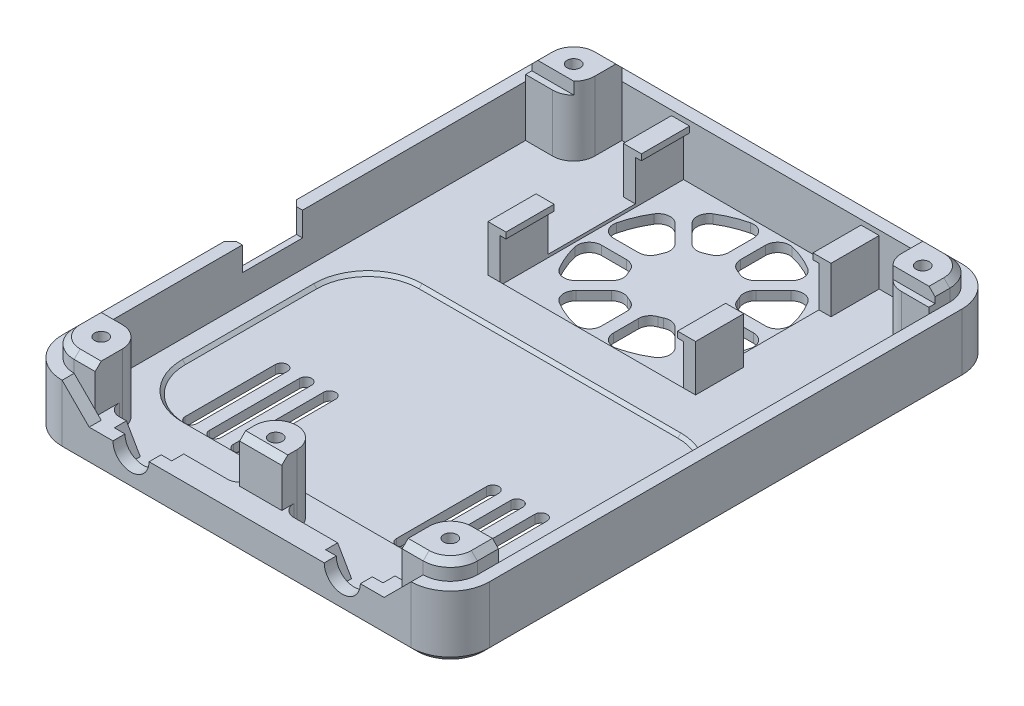
SolidWorks part; units mm, degrees
ref_plane "Front Plane" through (0, 0, 0) normal (0, 0, 1) x (1, 0, 0)
ref_plane "Top Plane" through (0, 0, 0) normal (0, 1, 0) x (1, 0, 0)
ref_plane "Right Plane" through (0, 0, 0) normal (1, 0, 0) x (0, 0, -1)
sketch "Sketch1" plane through (0, 0, 0) normal (0, 1, 0) x (1, 0, 0)
  line L0 (-33.8462, -25.5532) -> (31.1538, -25.5532)
  line L1 (-33.8462, 38.4468) -> (31.1538, 38.4468)
  line L2 (-33.8462, 38.4468) -> (-33.8462, 8.4468)
  line L3 (-33.8462, 8.4468) -> (31.1538, 8.4468)
  line L4 (31.1538, 38.4468) -> (31.1538, 8.4468)
  line L5 (-30.3462, 34.9468) -> (27.6538, 34.9468)
  line L6 (-30.3462, 34.9468) -> (-30.3462, 11.9468)
  line L7 (-30.3462, 11.9468) -> (27.6538, 11.9468)
  line L8 (27.6538, 34.9468) -> (27.6538, 11.9468)
  line L9 (-30.3462, 0.9468) -> (27.6538, 0.9468)
  line L10 (-30.3462, 0.9468) -> (-30.3462, -22.0532)
  line L11 (-33.8462, 4.4468) -> (31.1538, 4.4468)
  line L12 (-33.8462, 4.4468) -> (-33.8462, -25.5532)
  line L13 (-30.3462, -22.0532) -> (27.6538, -22.0532)
  line L14 (31.1538, 4.4468) -> (31.1538, -25.5532)
  line L15 (27.6538, 0.9468) -> (27.6538, -22.0532)
  line L16 (-37.9161, 25.3468) -> (-35.3276, 25.3468)
  line L17 (7.5538, 7.5472) -> (7.5538, 6.2645)
  line L18 (20.1538, 7.5472) -> (20.1538, 6.2645)
  dimension "D1" = 65
  dimension "D2" = 30
  dimension "D3" = 58
  dimension "D4" = 23
  dimension "D5" = 3.5
  dimension "D6" = 3.5
  dimension "D7" = 65
  dimension "D8" = 30
  dimension "D9" = 58
  dimension "D10" = 23
  dimension "D11" = 3.5
  dimension "D12" = 3.5
  dimension "D13" = 4
  dimension "D14" = 16.9
  dimension "D15" = 41.4
  dimension "D16" = 54
sketch "Sketch2" plane through (0, 0, 0) normal (0, 1, 0) x (1, 0, 0)
  line L0 (-33.8462, 38.4468) -> (-33.8462, 8.4468) construction
  line L1 (-30.3462, 39.4468) -> (27.6538, 39.4468)
  line L2 (-34.8462, 34.9468) -> (-34.8462, -43.5532)
  line L3 (-30.3462, -48.0532) -> (27.6538, -48.0532)
  line L4 (32.1538, 34.9468) -> (32.1538, -43.5532)
  line L5 (-33.8462, 38.4468) -> (31.1538, 38.4468) construction
  line L6 (31.1538, 38.4468) -> (31.1538, 8.4468) construction
  line L7 (-30.3462, 41.4468) -> (27.6538, 41.4468)
  line L8 (34.1538, 34.9468) -> (34.1538, -43.5532)
  line L9 (-30.3462, -50.0532) -> (27.6538, -50.0532)
  line L10 (-36.8462, 34.9468) -> (-36.8462, -43.5532)
  line L11 (-34.8462, 39.4468) -> (32.1538, 39.4468) construction
  line L12 (-34.8462, 39.4468) -> (-34.8462, -48.0532) construction
  line L13 (-36.8462, 41.4468) -> (-36.8462, -50.0532) construction
  line L14 (-36.8462, 41.4468) -> (34.1538, 41.4468) construction
  line L15 (32.1538, 39.4468) -> (32.1538, -48.0532) construction
  line L16 (34.1538, 41.4468) -> (34.1538, -50.0532) construction
  line L17 (-36.8462, -50.0532) -> (34.1538, -50.0532) construction
  line L18 (-34.8462, -48.0532) -> (32.1538, -48.0532) construction
  arc A0 (-30.3462, 39.4468) -> (-34.8462, 34.9468) centre (-30.3462, 34.9468) ccw
  arc A1 (-36.8462, 34.9468) -> (-30.3462, 41.4468) centre (-30.3462, 34.9468) cw
  arc A2 (32.1538, 34.9468) -> (27.6538, 39.4468) centre (27.6538, 34.9468) ccw
  arc A3 (34.1538, 34.9468) -> (27.6538, 41.4468) centre (27.6538, 34.9468) ccw
  arc A4 (27.6538, -50.0532) -> (34.1538, -43.5532) centre (27.6538, -43.5532) ccw
  arc A5 (-36.8462, -43.5532) -> (-30.3462, -50.0532) centre (-30.3462, -43.5532) ccw
  arc A6 (27.6538, -48.0532) -> (32.1538, -43.5532) centre (27.6538, -43.5532) ccw
  arc A7 (-30.3462, -48.0532) -> (-34.8462, -43.5532) centre (-30.3462, -43.5532) cw
  dimension "D6" = 4.5
  dimension "D7" = 6.5
  dimension "D8" = 4.5
  dimension "D9" = 6.5
  dimension "D10" = 6.5
  dimension "D11" = 4.5
  dimension "D1" = 1
  dimension "D2" = 1
  dimension "D3" = 1
  dimension "D4" = 87.5
  dimension "D5" = 2
extrude "Boss-Extrude1" add sketch "Sketch2" along normal blind 10.5
sketch "Sketch3" plane through (0, 0, 0) normal (0, 1, 0) x (1, 0, 0)
  line L0 (-30.3462, -48.0532) -> (27.6538, -48.0532)
  line L1 (-30.3462, 39.4468) -> (27.6538, 39.4468)
  line L2 (-34.8462, 34.9468) -> (-34.8462, -43.5532)
  line L4 (32.1538, 34.9468) -> (32.1538, -43.5532)
  arc A0 (27.6538, -48.0532) -> (32.1538, -43.5532) centre (27.6538, -43.5532) ccw
  arc A1 (-34.8462, -43.5532) -> (-30.3462, -48.0532) centre (-30.3462, -43.5532) ccw
  arc A2 (32.1538, 34.9468) -> (27.6538, 39.4468) centre (27.6538, 34.9468) ccw
  arc A3 (-30.3462, 39.4468) -> (-34.8462, 34.9468) centre (-30.3462, 34.9468) ccw
  point P15 (-34.8462, 39.4468)
  dimension "D1" = 4.5
  dimension "D2" = 87.5
extrude "Boss-Extrude2" add sketch "Sketch3" along normal blind 2
sketch "Sketch6" plane through (0, 2, 0) normal (0, 1, 0) x (1, 0, 0)
  line L3 (-34.8462, 34.9468) -> (-34.8462, -43.5532) construction
  line L5 (-26.8462, 34.9468) -> (-26.8462, 39.4468)
  line L6 (27.6538, 39.4468) -> (-30.3462, 39.4468) construction
  line L7 (-26.8462, 39.4468) -> (-30.3462, 39.4468)
  line L8 (-30.3462, 31.4468) -> (-34.8462, 31.4468)
  line L9 (-34.8462, 31.4468) -> (-34.8462, 34.9468)
  line L10 (24.1538, 34.9468) -> (24.1538, 39.4468)
  line L11 (24.1538, 39.4468) -> (27.6538, 39.4468)
  line L12 (27.6538, 31.4468) -> (32.1538, 31.4468)
  line L13 (32.1538, -43.5532) -> (32.1538, 34.9468) construction
  line L14 (32.1538, 31.4468) -> (32.1538, 34.9468)
  arc A0 (-30.3462, 31.4468) -> (-26.8462, 34.9468) centre (-30.3462, 34.9468) ccw
  arc A1 (24.1538, 34.9468) -> (27.6538, 31.4468) centre (27.6538, 34.9468) ccw
  arc A4 (-30.3462, 39.4468) -> (-34.8462, 34.9468) centre (-30.3462, 34.9468) ccw
  arc A5 (32.1538, 34.9468) -> (27.6538, 39.4468) centre (27.6538, 34.9468) ccw
  dimension "D1" = 4.5
  dimension "D2" = 4.5
extrude "Boss-Extrude4" add sketch "Sketch6" along normal blind 11.5
sketch "Sketch7" plane through (0, 0, 50.0532) normal (0, 0, 1) x (1, 0, 0)
  line L0 (27.6538, 10.5) -> (-30.3462, 10.5)
  line L2 (16.2046, 6) -> (16.2046, 3) construction
  line L3 (-18.8969, 6) -> (-18.8969, 3) construction
  line L4 (-1.3462, 10.5) -> (-1.3462, 13.2512) construction
  line L5 (-30.3462, 10.5) -> (27.6538, 10.5) construction
  line L20 (27.6538, 10.5) -> (23.1538, 6)
  line L21 (23.1538, 6) -> (19.2046, 6)
  line L22 (13.2046, 6) -> (-15.8969, 6)
  line L23 (-25.8462, 6) -> (-21.8969, 6)
  line L24 (-30.3462, 10.5) -> (-25.8462, 6)
  arc A0 (-21.8969, 6) -> (-15.8969, 6) centre (-18.8969, 6) ccw
  arc A1 (13.2046, 6) -> (19.2046, 6) centre (16.2046, 6) ccw
  dimension "D3" = 45
  dimension "D1" = 4.5
  dimension "D4" = 3
  dimension "D5" = 3
  dimension "D2" = 45
  dimension "D6" = 4.5
  dimension "D7" = 4.5
sketch "Sketch8" plane through (0, 2, 0) normal (0, 1, 0) x (1, 0, 0)
  line L0 (-4.8462, -43.5532) -> (-4.8462, -48.0532)
  line L2 (-30.3462, -48.0532) -> (27.6538, -48.0532) construction
  line L4 (-4.8462, -48.0532) -> (2.1538, -48.0532)
  line L5 (2.1538, -48.0532) -> (2.1538, -43.5532)
  line L9 (32.1538, -40.0532) -> (32.1538, -43.5532)
  line L10 (27.6538, -40.0532) -> (32.1538, -40.0532)
  line L11 (24.1538, -48.0532) -> (27.6538, -48.0532)
  line L12 (24.1538, -43.5532) -> (24.1538, -48.0532)
  line L13 (-34.8462, -40.0532) -> (-34.8462, -43.5532)
  line L14 (-30.3462, -40.0532) -> (-34.8462, -40.0532)
  line L15 (-26.8462, -48.0532) -> (-30.3462, -48.0532)
  line L16 (-26.8462, -43.5532) -> (-26.8462, -48.0532)
  arc A0 (2.1538, -43.5532) -> (-4.8462, -43.5532) centre (-1.3462, -43.5532) ccw
  arc A4 (32.1538, -43.5532) -> (27.6538, -48.0532) centre (27.6538, -43.5532) cw
  arc A5 (-30.3462, -48.0532) -> (-34.8462, -43.5532) centre (-30.3462, -43.5532) cw
  arc A6 (24.1538, -43.5532) -> (27.6538, -40.0532) centre (27.6538, -43.5532) cw
  arc A7 (-30.3462, -40.0532) -> (-26.8462, -43.5532) centre (-30.3462, -43.5532) cw
extrude "Boss-Extrude6" add sketch "Sketch8" along normal up to surface (11.5 mm away) up to face at (-30.714, 13.5, -35.3147)
extrude "Cut-Extrude1" cut sketch "Sketch7" against normal up to vertex (2 mm away) up to point (-15.8462, 10.5, 48.0532)
sketch "Sketch9" plane through (-36.8462, 0, 0) normal (-1, 0, 0) x (0, 0, 1)
  line L1 (15.6113, 10.5) -> (5.6113, 10.5)
  line L2 (15.6113, 10.5) -> (15.6113, 6.5)
  line L3 (15.6113, 6.5) -> (5.6113, 6.5)
  line L4 (5.6113, 10.5) -> (5.6113, 6.5)
  line L5 (15.6113, 10.5) -> (5.6113, 6.5) construction
  line L6 (15.6113, 6.5) -> (5.6113, 10.5) construction
  point P0 (10.6113, 8.5)
  dimension "D1" = 10
  dimension "D2" = 4
extrude "Cut-Extrude2" cut sketch "Sketch9" against normal up to next
chamfer "Chamfer1" distance 1 angle 45 3 edges at (-36.8462, 8.5, 5.6113) (-36.8462, 8.5, 15.6113) (-36.8462, 6.5, 10.6113)
chamfer "Chamfer2" distance 1 angle 45 8 edges at (-36.8462, 0, 4.3032) (-34.9423, 0, 48.1493) (-34.9423, 0, -39.543) (-1.3462, 0, 50.0532) (-1.3462, 0, -41.4468) (32.25, 0, 48.1493) (32.25, 0, -39.543) (34.1538, 0, 4.3032)
sketch "Sketch19" plane through (0, 0, 48.0532) normal (0, 0, -1) x (-1, 0, 0)
  line L0 (24.6458, 6) -> (23.6607, 6)
  line L1 (14.1331, 6) -> (16.515, 1.8744)
  line L2 (16.515, 1.8744) -> (21.2788, 1.8744)
  line L3 (21.2788, 1.8744) -> (23.6607, 6)
  line L4 (-11.4408, 6) -> (-10.4558, 6)
  line L5 (-20.9684, 6) -> (-21.9535, 6)
  line L6 (24.6458, 6) -> (26.8462, 6)
  line L7 (-20.9684, 6) -> (-18.5865, 1.8744)
  line L8 (-18.5865, 1.8744) -> (-13.8227, 1.8744)
  line L9 (-13.8227, 1.8744) -> (-11.4408, 6)
  line L10 (26.8462, 7) -> (26.8462, 2) construction
  line L11 (26.8462, 6) -> (26.8462, 2)
  line L12 (26.8462, 2) -> (21.3513, 2)
  line L13 (13.1481, 6) -> (14.1331, 6)
  line L14 (26.8462, 2) -> (4.8462, 2) construction
  line L15 (22.4698, 8.0628) -> (21.3151, 10.0628) [skipped]
  line L16 (16.3625, 9.8613) -> (15.2078, 7.8613) [skipped]
  line L17 (20.9737, 10.1256) -> (16.3549, 10.1256) [skipped]
  line L18 (-12.6318, 8.0628) -> (-13.7865, 10.0628) [skipped]
  line L19 (-16.2046, 10.1256) -> (-18.514, 10.1256) [skipped]
  line L20 (-18.7391, 9.8613) -> (-19.8938, 7.8613) [skipped]
  line L21 (13.1481, 6) -> (-10.4558, 6)
  line L22 (-21.9535, 6) -> (-24.1538, 6)
  line L23 (-24.1538, 7) -> (-24.1538, 2) construction
  line L24 (-24.1538, 6) -> (-24.1538, 2)
  line L25 (-24.1538, 2) -> (-18.659, 2)
  line L26 (-13.7502, 2) -> (16.4425, 2)
  arc A0 (15.3241, 3.9372) -> (22.4698, 3.9372) centre (18.8969, 6) ccw construction
  arc A1 (-19.7775, 3.9372) -> (-12.6318, 3.9372) centre (-16.2046, 6) ccw construction
extrude "Boss-Extrude7" add sketch "Sketch19" along normal blind 2
sketch "Sketch21" plane through (0, 13.5, 0) normal (0, 1, 0) x (1, 0, 0)
  line L0 (-34.8462, 34.9468) -> (-34.8462, 31.4468) construction
  line L1 (-34.8462, 32.4905) -> (32.1538, 32.4905)
  line L2 (-34.8462, 32.4905) -> (-34.8462, 31.4468)
  line L3 (-34.8462, 31.4468) -> (32.1538, 31.4468)
  line L4 (32.1538, 32.4905) -> (32.1538, 31.4468)
extrude "Cut-Extrude4" cut sketch "Sketch21" against normal blind 2
sketch "Sketch22" plane through (0, 2, 0) normal (0, 1, 0) x (1, 0, 0)
  line L0 (-34.8462, 31.4468) -> (-34.8462, -40.0532) construction
  line L1 (-22.8462, 3.2594) -> (20.1538, 3.2594)
  line L2 (-32.8462, -6.7406) -> (-32.8462, -28.5682)
  line L3 (-22.8462, -38.5682) -> (20.1538, -38.5682)
  line L4 (30.1538, -6.7406) -> (30.1538, -28.5682)
  line L5 (32.1538, -40.0532) -> (32.1538, 31.4468) construction
  arc A0 (-22.8462, -38.5682) -> (-32.8462, -28.5682) centre (-22.8462, -28.5682) cw
  arc A1 (20.1538, -38.5682) -> (30.1538, -28.5682) centre (20.1538, -28.5682) ccw
  arc A2 (20.1538, 3.2594) -> (30.1538, -6.7406) centre (20.1538, -6.7406) cw
  arc A3 (-22.8462, 3.2594) -> (-32.8462, -6.7406) centre (-22.8462, -6.7406) ccw
  dimension "D3" = 10
  dimension "D1" = 2
  dimension "D2" = 2
extrude "Cut-Extrude5" cut sketch "Sketch22" against normal blind 0.5
chamfer "Chamfer4" distance 1.5 angle 45 8 edges at (-1.3462, 1.5, 38.5682) (27.2249, 1.5, 35.6392) (-29.9172, 1.5, 35.6392) (30.1538, 1.5, 17.6544) (-32.8462, 1.5, 17.6544) (27.2249, 1.5, -0.3305) (-29.9172, 1.5, -0.3305) (-1.3462, 1.5, -3.2594)
chamfer "Chamfer5" distance 1 angle 45 3 edges at (32.1538, 13.5, -33.7187) (25.9038, 13.5, -39.4468) (30.8358, 13.5, -38.1288)
chamfer "Chamfer6" distance 1 angle 45 3 edges at (-28.5962, 13.5, -39.4468) (-34.8462, 13.5, -33.7187) (-33.5281, 13.5, -38.1288)
chamfer "Chamfer7" distance 1 angle 45 6 edges at (25.9038, 13.5, 48.0532) (32.1538, 13.5, 41.8032) (30.8358, 13.5, 46.7351) (-34.8462, 13.5, 41.8032) (-28.5962, 13.5, 48.0532) (-33.5281, 13.5, 46.7351)
hole_wizard "Ø2.2 (2.2) Diameter Hole1" positions "Sketch24" profile "Sketch25" hole size "Ø2.2" standard "ANSI Metric"
sketch "Sketch24" plane through (0, 13.5, 0) normal (0, 1, 0) x (1, 0, 0)
  point P0 (-30.3462, -43.5532)
  point P4 (27.6538, -43.5532)
  point P10 (27.6538, 34.9468)
  point P14 (-30.3462, 34.9468)
  point P17 (-1.3462, -43.5532)
sketch "Sketch25" plane through (-30.3462, 13.5, 43.5532) normal (1, 0, 0) x (0, 0, 1)
  line L0 (0, 0) -> (0, 12.1609)
  line L1 (0, 12.1609) -> (1.1, 11.5)
  line L2 (1.1, 11.5) -> (1.1, 0)
  line L5 (1.1, 0) -> (0, 0)
  line L10 (0, 12.1609) -> (-1.1, 11.5) construction
  line L11 (0, -6.35) -> (0, 107.95) construction
  dimension "Hole Dia." = 2.2
  dimension "Hole Depth" = 11.5
  dimension "Drill Angle" = 118
sketch "Sketch27" plane through (0, 13.5, 0) normal (0, 1, 0) x (1, 0, 0)
  line L1 (-4.8462, -46.0532) -> (2.1538, -46.0532)
  line L2 (-4.8462, -46.0532) -> (-4.8462, -48.0532)
  line L3 (-4.8462, -48.0532) -> (2.1538, -48.0532)
  line L4 (2.1538, -46.0532) -> (2.1538, -48.0532)
extrude "Cut-Extrude6" cut sketch "Sketch27" against normal up to surface (7.5 mm away) up to face at (-1.3462, 6, 47.7198)
fillet "Fillet1" radius 2 4 edges at (-26.8462, 4, 46.0532) (2.1538, 4, 46.0532) (-4.8462, 4, 46.0532) (24.1538, 4, 46.0532)
chamfer "Chamfer8" distance 1 angle 45 1 edges at (-1.3462, 13.5, 46.0532)
sketch "Sketch28" plane through (0, 0, 0) normal (0, -1, 0) x (1, 0, 0)
  line L0 (-18.8969, 36.0532) -> (-18.8969, 21.0532) construction
  line L1 (-17.8969, 36.0532) -> (-17.8969, 21.0532)
  line L2 (-19.8969, 36.0532) -> (-19.8969, 21.0532)
  line L3 (-18.8969, 48.0532) -> (-18.8969, 15.8895) construction
  line L4 (-21.3513, 48.0532) -> (-16.4425, 48.0532) construction
  line L5 (-15.8969, 50.0532) -> (-21.8969, 50.0532) construction
  line L6 (-22.8969, 36.0532) -> (-22.8969, 21.0532) construction
  line L7 (-21.8969, 36.0532) -> (-21.8969, 21.0532)
  line L8 (-23.8969, 36.0532) -> (-23.8969, 21.0532)
  line L9 (-14.8969, 36.0532) -> (-14.8969, 21.0532) construction
  line L10 (-13.8969, 36.0532) -> (-13.8969, 21.0532)
  line L11 (-15.8969, 36.0532) -> (-15.8969, 21.0532)
  line L12 (16.2046, 48.0532) -> (16.2046, 15.8895) construction
  line L13 (16.2046, 36.0532) -> (16.2046, 21.0532) construction
  line L14 (17.2046, 36.0532) -> (17.2046, 21.0532)
  line L15 (15.2046, 36.0532) -> (15.2046, 21.0532)
  line L16 (12.2046, 36.0532) -> (12.2046, 21.0532) construction
  line L17 (13.2046, 36.0532) -> (13.2046, 21.0532)
  line L18 (11.2046, 36.0532) -> (11.2046, 21.0532)
  line L19 (20.2046, 36.0532) -> (20.2046, 21.0532) construction
  line L20 (21.2046, 36.0532) -> (21.2046, 21.0532)
  line L21 (19.2046, 36.0532) -> (19.2046, 21.0532)
  arc A0 (-17.8969, 36.0532) -> (-19.8969, 36.0532) centre (-18.8969, 36.0532) ccw
  arc A1 (-19.8969, 21.0532) -> (-17.8969, 21.0532) centre (-18.8969, 21.0532) ccw
  arc A2 (-21.8969, 36.0532) -> (-23.8969, 36.0532) centre (-22.8969, 36.0532) ccw
  arc A3 (-23.8969, 21.0532) -> (-21.8969, 21.0532) centre (-22.8969, 21.0532) ccw
  arc A4 (-13.8969, 36.0532) -> (-15.8969, 36.0532) centre (-14.8969, 36.0532) ccw
  arc A5 (-15.8969, 21.0532) -> (-13.8969, 21.0532) centre (-14.8969, 21.0532) ccw
  arc A6 (17.2046, 36.0532) -> (15.2046, 36.0532) centre (16.2046, 36.0532) ccw
  arc A7 (15.2046, 21.0532) -> (17.2046, 21.0532) centre (16.2046, 21.0532) ccw
  arc A8 (13.2046, 36.0532) -> (11.2046, 36.0532) centre (12.2046, 36.0532) ccw
  arc A9 (11.2046, 21.0532) -> (13.2046, 21.0532) centre (12.2046, 21.0532) ccw
  arc A10 (21.2046, 36.0532) -> (19.2046, 36.0532) centre (20.2046, 36.0532) ccw
  arc A11 (19.2046, 21.0532) -> (21.2046, 21.0532) centre (20.2046, 21.0532) ccw
  point P2 (-18.8969, 28.5532)
  point P11 (-18.8969, 50.0532)
  point P18 (-22.8969, 28.5532)
  point P24 (-14.8969, 28.5532)
  point P30 (16.2046, 28.5532)
  point P40 (12.2046, 28.5532)
  point P46 (20.2046, 28.5532)
  dimension "D1" = 14
  dimension "D2" = 2
  dimension "D3" = 2
extrude "Cut-Extrude7" cut sketch "Sketch28" against normal through all
sketch "Sketch29" plane through (0, 2, 0) normal (0, 1, 0) x (1, 0, 0)
  line L1 (-16.5962, 39.4468) -> (13.9038, 39.4468)
  line L2 (-16.5962, 39.4468) -> (-16.5962, 8.9468)
  line L3 (-16.5962, 8.9468) -> (13.9038, 8.9468)
  line L4 (13.9038, 39.4468) -> (13.9038, 8.9468)
  dimension "D1" = 30.5
  dimension "D2" = 30.5
extrude "Cut-Extrude8" cut sketch "Sketch29" against normal blind 0.5
sketch "Sketch30" plane through (0, 2, 0) normal (0, 1, 0) x (1, 0, 0)
  line L0 (-1.3462, 8.9468) -> (-1.3462, 39.4468) construction
  line L1 (13.9038, 39.4468) -> (15.9038, 39.4468)
  line L2 (13.9038, 39.4468) -> (13.9038, 31.4468)
  line L3 (13.9038, 31.4468) -> (15.9038, 31.4468)
  line L4 (15.9038, 39.4468) -> (15.9038, 31.4468)
  line L5 (-16.5962, 8.9468) -> (13.9038, 8.9468) construction
  line L6 (-16.5962, 24.1968) -> (13.9038, 24.1968) construction
  line L7 (-16.5962, 39.4468) -> (-16.5962, 8.9468) construction
  line L8 (13.9038, 8.9468) -> (13.9038, 39.4468) construction
  line L9 (-18.5962, 39.4468) -> (-18.5962, 31.4468)
  line L10 (-16.5962, 31.4468) -> (-18.5962, 31.4468)
  line L11 (-16.5962, 39.4468) -> (-16.5962, 31.4468)
  line L12 (-16.5962, 39.4468) -> (-18.5962, 39.4468)
  line L13 (-16.5962, 8.9468) -> (-18.5962, 8.9468)
  line L14 (-16.5962, 8.9468) -> (-16.5962, 16.9468)
  line L15 (-16.5962, 16.9468) -> (-18.5962, 16.9468)
  line L16 (-18.5962, 8.9468) -> (-18.5962, 16.9468)
  line L17 (15.9038, 8.9468) -> (15.9038, 16.9468)
  line L18 (13.9038, 16.9468) -> (15.9038, 16.9468)
  line L19 (13.9038, 8.9468) -> (13.9038, 16.9468)
  line L20 (13.9038, 8.9468) -> (15.9038, 8.9468)
  dimension "D1" = 8
  dimension "D2" = 2
extrude "Boss-Extrude8" add sketch "Sketch30" along normal blind 7.7
sketch "Sketch32" plane through (0, 9.7, 0) normal (0, 1, 0) x (1, 0, 0)
  line L0 (13.9038, 39.4468) -> (-16.5962, 39.4468) construction
  line L1 (13.9038, 31.4468) -> (12.9038, 31.4468)
  line L2 (13.9038, 31.4468) -> (13.9038, 39.4468)
  line L3 (13.9038, 39.4468) -> (12.9038, 39.4468)
  line L4 (12.9038, 31.4468) -> (12.9038, 39.4468)
  line L5 (-1.3462, 8.9468) -> (-1.3462, 39.4468) construction
  line L6 (-16.5962, 8.9468) -> (13.9038, 8.9468) construction
  line L7 (24.1538, 39.4468) -> (-26.8462, 39.4468) construction
  line L8 (-16.5962, 24.1968) -> (13.9038, 24.1968) construction
  line L9 (-16.5962, 31.4468) -> (-16.5962, 16.9468) construction
  line L10 (13.9038, 16.9468) -> (13.9038, 31.4468) construction
  line L11 (-15.5962, 31.4468) -> (-15.5962, 39.4468)
  line L12 (-16.5962, 39.4468) -> (-15.5962, 39.4468)
  line L13 (-16.5962, 31.4468) -> (-16.5962, 39.4468)
  line L14 (-16.5962, 31.4468) -> (-15.5962, 31.4468)
  line L15 (-16.5962, 16.9468) -> (-15.5962, 16.9468)
  line L16 (-16.5962, 16.9468) -> (-16.5962, 8.9468)
  line L17 (-16.5962, 8.9468) -> (-15.5962, 8.9468)
  line L18 (-15.5962, 16.9468) -> (-15.5962, 8.9468)
  line L19 (12.9038, 16.9468) -> (12.9038, 8.9468)
  line L20 (13.9038, 8.9468) -> (12.9038, 8.9468)
  line L21 (13.9038, 16.9468) -> (13.9038, 8.9468)
  line L22 (13.9038, 16.9468) -> (12.9038, 16.9468)
  dimension "D1" = 1
extrude "Boss-Extrude10" add sketch "Sketch32" against normal blind 1
sketch "Sketch33" plane through (0, 1.5, 0) normal (0, 1, 0) x (1, 0, 0)
  line L0 (-1.3462, 39.1968) -> (-1.3462, 31.1968) construction
  line L1 (-2.3462, 36.846) -> (-2.3462, 32.6821)
  line L2 (-0.3462, 36.846) -> (-0.3462, 32.6821)
  line L3 (6.891, 33.8482) -> (3.9467, 30.904)
  line L4 (8.3052, 32.434) -> (5.361, 29.4897)
  line L5 (11.303, 25.1968) -> (7.1391, 25.1968)
  line L6 (11.303, 23.1968) -> (7.1391, 23.1968)
  line L7 (8.3052, 15.9597) -> (5.361, 18.904)
  line L8 (6.891, 14.5455) -> (3.9467, 17.4897)
  line L9 (-0.3462, 11.5477) -> (-0.3462, 15.7116)
  line L10 (-2.3462, 11.5477) -> (-2.3462, 15.7116)
  line L11 (-9.5833, 14.5455) -> (-6.639, 17.4897)
  line L12 (-10.9975, 15.9597) -> (-8.0533, 18.904)
  line L13 (-13.9953, 23.1968) -> (-9.8314, 23.1968)
  line L14 (-13.9953, 25.1968) -> (-9.8314, 25.1968)
  line L15 (-10.9975, 32.434) -> (-8.0533, 29.4897)
  line L16 (-9.5833, 33.8482) -> (-6.639, 30.904)
  line L17 (-0.3462, 39.1968) -> (-0.3462, 31.1968) construction
  line L18 (-2.3462, 39.1968) -> (-2.3462, 31.1968) construction
  arc A0 (-7.6627, 27.2136) -> (-7.9458, 26.5302) centre (-1.3462, 24.1968) ccw
  arc A1 (-15.9413, 20.7353) -> (-14.1141, 16.3242) centre (-1.3462, 24.1968) ccw
  arc A2 (1.6706, 30.5134) -> (0.9872, 30.7965) centre (-1.3462, 24.1968) ccw
  arc A3 (5.2535, 26.5302) -> (4.9704, 27.2136) centre (-1.3462, 24.1968) ccw
  arc A4 (4.9704, 21.1801) -> (5.2535, 21.8635) centre (-1.3462, 24.1968) ccw
  arc A5 (0.9872, 17.5972) -> (1.6706, 17.8803) centre (-1.3462, 24.1968) ccw
  arc A6 (-4.3629, 17.8803) -> (-3.6795, 17.5972) centre (-1.3462, 24.1968) ccw
  arc A7 (-7.9458, 21.8635) -> (-7.6627, 21.1801) centre (-1.3462, 24.1968) ccw
  arc A8 (-14.1141, 32.0695) -> (-15.9413, 27.6584) centre (-1.3462, 24.1968) ccw
  arc A9 (-4.8077, 38.792) -> (-9.2188, 36.9648) centre (-1.3462, 24.1968) ccw
  arc A10 (6.5265, 36.9648) -> (2.1154, 38.792) centre (-1.3462, 24.1968) ccw
  arc A11 (13.249, 27.6584) -> (11.4218, 32.0695) centre (-1.3462, 24.1968) ccw
  arc A12 (11.4218, 16.3242) -> (13.249, 20.7353) centre (-1.3462, 24.1968) ccw
  arc A13 (2.1154, 9.6017) -> (6.5265, 11.4289) centre (-1.3462, 24.1968) ccw
  arc A14 (-9.2188, 11.4289) -> (-4.8077, 9.6017) centre (-1.3462, 24.1968) ccw
  arc A15 (-6.9522, 28.3887) -> (-8.2744, 25.1968) centre (-1.3462, 24.1968) ccw
  arc A16 (-3.6795, 30.7965) -> (-4.3629, 30.5134) centre (-1.3462, 24.1968) ccw
  arc A17 (2.8457, 29.8029) -> (-0.3462, 31.1251) centre (-1.3462, 24.1968) ccw
  arc A18 (5.582, 25.1968) -> (4.2599, 28.3887) centre (-1.3462, 24.1968) ccw
  arc A19 (4.2599, 20.005) -> (5.582, 23.1968) centre (-1.3462, 24.1968) ccw
  arc A20 (-0.3462, 17.2686) -> (2.8457, 18.5908) centre (-1.3462, 24.1968) ccw
  arc A21 (-5.538, 18.5908) -> (-2.3462, 17.2686) centre (-1.3462, 24.1968) ccw
  arc A22 (-8.2744, 23.1968) -> (-6.9522, 20.005) centre (-1.3462, 24.1968) ccw
  arc A23 (-2.3462, 36.846) -> (-4.8077, 38.792) centre (-4.3462, 36.846) ccw
  arc A24 (-3.6795, 30.7965) -> (-2.3462, 32.6821) centre (-4.3462, 32.6821) ccw
  arc A25 (-6.639, 30.904) -> (-4.3629, 30.5134) centre (-5.2248, 32.3182) ccw
  arc A26 (-9.5833, 33.8482) -> (-9.2188, 36.9648) centre (-8.1691, 35.2624) cw
  arc A27 (1.6706, 30.5134) -> (3.9467, 30.904) centre (2.5325, 32.3182) ccw
  arc A28 (6.5265, 36.9648) -> (6.891, 33.8482) centre (5.4768, 35.2624) cw
  arc A29 (0.9872, 30.7965) -> (-0.3462, 32.6821) centre (1.6538, 32.6821) cw
  arc A30 (-0.3462, 36.846) -> (2.1154, 38.792) centre (1.6538, 36.846) cw
  arc A31 (-7.6627, 27.2136) -> (-8.0533, 29.4897) centre (-9.4675, 28.0755) ccw
  arc A32 (-7.9458, 26.5302) -> (-9.8314, 25.1968) centre (-9.8314, 27.1968) cw
  arc A33 (-7.9458, 21.8635) -> (-9.8314, 23.1968) centre (-9.8314, 21.1968) ccw
  arc A34 (-7.6627, 21.1801) -> (-8.0533, 18.904) centre (-9.4675, 20.3182) cw
  arc A35 (-6.639, 17.4897) -> (-4.3629, 17.8803) centre (-5.2248, 16.0755) cw
  arc A36 (-3.6795, 17.5972) -> (-2.3462, 15.7116) centre (-4.3462, 15.7116) cw
  arc A37 (0.9872, 17.5972) -> (-0.3462, 15.7116) centre (1.6538, 15.7116) ccw
  arc A38 (1.6706, 17.8803) -> (3.9467, 17.4897) centre (2.5325, 16.0755) cw
  arc A39 (4.9704, 21.1801) -> (5.361, 18.904) centre (6.7752, 20.3182) ccw
  arc A40 (5.2535, 21.8635) -> (7.1391, 23.1968) centre (7.1391, 21.1968) cw
  arc A41 (5.2535, 26.5302) -> (7.1391, 25.1968) centre (7.1391, 27.1968) ccw
  arc A42 (4.9704, 27.2136) -> (5.361, 29.4897) centre (6.7752, 28.0755) cw
  arc A43 (8.3052, 32.434) -> (11.4218, 32.0695) centre (9.7194, 31.0198) cw
  arc A44 (13.249, 27.6584) -> (11.303, 25.1968) centre (11.303, 27.1968) cw
  arc A45 (11.303, 23.1968) -> (13.249, 20.7353) centre (11.303, 21.1968) cw
  arc A46 (11.4218, 16.3242) -> (8.3052, 15.9597) centre (9.7194, 17.3739) cw
  arc A47 (6.891, 14.5455) -> (6.5265, 11.4289) centre (5.4768, 13.1313) cw
  arc A48 (2.1154, 9.6017) -> (-0.3462, 11.5477) centre (1.6538, 11.5477) cw
  arc A49 (-2.3462, 11.5477) -> (-4.8077, 9.6017) centre (-4.3462, 11.5477) cw
  arc A50 (-9.2188, 11.4289) -> (-9.5833, 14.5455) centre (-8.1691, 13.1313) cw
  arc A51 (-10.9975, 15.9597) -> (-14.1141, 16.3242) centre (-12.4117, 17.3739) cw
  arc A52 (-15.9413, 20.7353) -> (-13.9953, 23.1968) centre (-13.9953, 21.1968) cw
  arc A53 (-13.9953, 25.1968) -> (-15.9413, 27.6584) centre (-13.9953, 27.1968) cw
  arc A54 (-14.1141, 32.0695) -> (-10.9975, 32.434) centre (-12.4117, 31.0198) cw
  point P40 (-1.3462, 24.1968)
  dimension "D1" = 1
  dimension "D2" = 1
  dimension "D3" = 8
  dimension "D4" = 2
  dimension "D5" = 2
  dimension "D6" = 2
  dimension "D7" = 2
extrude "Cut-Extrude9" cut sketch "Sketch33" against normal up to next contours A54 A8 A53 L14 A32 A0 A31 L15 | A26 L16 A25 A16 A24 L1 A23 A9 | A30 L2 A29 A2 A27 L3 A28 A10 | A44 A11 A43 L4 A42 A3 A41 L5 | A46 A12 A45 L6 A40 A4 A39 L7 | A48 A13 A47 L8 A38 A5 A37 L9 | A50 A14 A49 L10 A36 A6 A35 L11 | A52 A1 A51 L12 A34 A7 A33 L13
